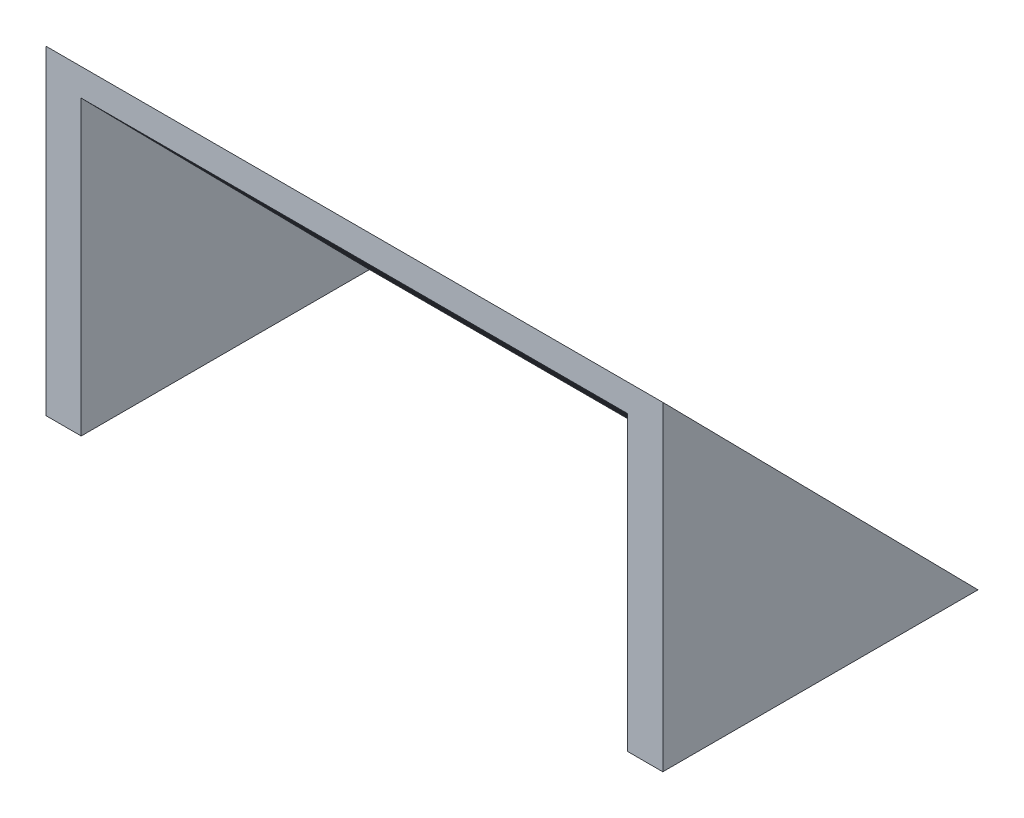
SolidWorks part; units mm, degrees
ref_plane "Přední rovina" through (0, 0, 0) normal (0, 0, 1) x (1, 0, 0)
ref_plane "Horní rovina" through (0, 0, 0) normal (0, 1, 0) x (1, 0, 0)
ref_plane "Pravá rovina" through (0, 0, 0) normal (1, 0, 0) x (0, 0, -1)
sketch "Skica1" plane through (0, 0, 0) normal (1, 0, 0) x (0, 0, -1)
  line L0 (0, 0) -> (0, 20)
  line L1 (0, 20) -> (19.7, 0)
  line L2 (19.7, 0) -> (0, 0)
  dimension "D1" = 19.7
  dimension "20" = 20
extrude "Přidat vysunutím1" add sketch "Skica1" along normal blind 2.2
sketch "Skica2" plane through (0, 9.8489, -9.9989) normal (0, 0.7017, -0.7124) x (-1, 0, 0)
  line L1 (-2.2, 14.2486) -> (-37.35, 14.2486)
  line L2 (-2.2, 14.2486) -> (-2.2, -13.8243)
  line L3 (-2.2, -13.8243) -> (-37.35, -13.8243)
  line L4 (-37.35, 14.2486) -> (-37.35, -13.8243)
  dimension "D1" = 35.15
extrude "Přidat vysunutím2" add sketch "Skica2" against normal blind 1.2
pattern_linear "LinPole1" count 2 spacing 36.35 along (1, 0, 0) of "Přidat vysunutím1"
sketch "Skica3" plane through (38.55, 0, 0) normal (1, 0, 0) x (0, 0, -1)
  line L0 (0, 20) -> (0, 0) construction
  line L1 (0, 16.835) -> (-2.4685, 16.835)
  line L2 (0, 16.835) -> (0, 21.1727)
  line L3 (0, 21.1727) -> (-2.4685, 21.1727)
  line L4 (-2.4685, 16.835) -> (-2.4685, 21.1727)
  line L5 (0, 0) -> (19.7, 0) construction
  line L6 (16.8501, 0) -> (22.214, 0)
  line L7 (16.8501, 0) -> (16.8501, -3.3952)
  line L8 (16.8501, -3.3952) -> (22.214, -3.3952)
  line L9 (22.214, 0) -> (22.214, -3.3952)
extrude "Odebrat vysunutím1" cut sketch "Skica3" against normal through all
